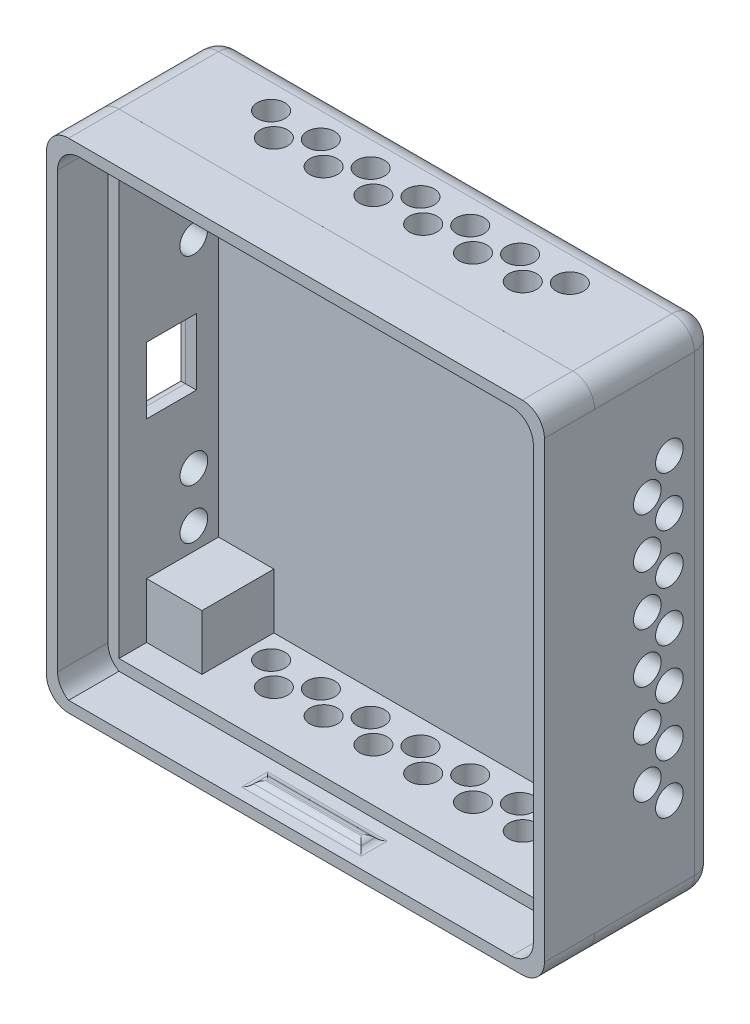
SolidWorks part; units mm, degrees
ref_plane "Piano frontale" through (0, 0, 0) normal (0, 0, 1) x (1, 0, 0)
ref_plane "Piano superiore" through (0, 0, 0) normal (0, 1, 0) x (1, 0, 0)
ref_plane "Piano destro" through (0, 0, 0) normal (1, 0, 0) x (0, 0, -1)
sketch "Schizzo2" plane through (0, 0, 0) normal (0, 0, 1) x (1, 0, 0)
  line L1 (0, 0) -> (45, 0)
  line L2 (0, 0) -> (0, 45)
  line L3 (0, 45) -> (45, 45)
  line L4 (45, 0) -> (45, 45)
  dimension "D1" = 45
  dimension "D2" = 45
extrude "Estrusione-Estrusione2" add sketch "Schizzo2" along normal blind 11
shell "Svuota1" thickness 2 removed face at (22.5, 22.5, 11)
fillet "Raccordo1" radius 2 4 edges at (45, 45, 5.5) (45, 0, 5.5) (0, 0, 5.5) (0, 45, 5.5)
fillet "Raccordo2" radius 2 8 edges at (44.4142, 0.5858, 0) (22.5, 0, 0) (0.5858, 0.5858, 0) (0, 22.5, 0) (0.5858, 44.4142, 0) (22.5, 45, 0) (44.4142, 44.4142, 0) (45, 22.5, 0)
sketch "Schizzo3" plane through (0, 0, 2) normal (0, 0, 1) x (1, 0, 0)
  line L0 (43, 43) -> (2, 43) construction
  line L1 (2, 43) -> (7, 43)
  line L2 (2, 43) -> (2, 38)
  line L3 (2, 38) -> (7, 38)
  line L4 (7, 43) -> (7, 38)
  line L5 (43, 43) -> (2, 43) construction
  dimension "D1" = 5
  dimension "D2" = 5
extrude "Estrusione-Estrusione3" add sketch "Schizzo3" along normal blind 6.5
sketch "Schizzo4" plane through (0, 0, 2) normal (0, 0, 1) x (1, 0, 0)
  line L1 (43, 2) -> (38, 2)
  line L2 (43, 2) -> (43, 7)
  line L3 (43, 7) -> (38, 7)
  line L4 (38, 2) -> (38, 7)
  dimension "D1" = 5
  dimension "D2" = 5
extrude "Estrusione-Estrusione4" add sketch "Schizzo4" along normal blind 6.5
fillet "Raccordo3" radius 4 2 edges at (38, 7, 5.25) (7, 38, 5.25)
sketch "Schizzo5" plane through (0, 0, 2) normal (0, 0, 1) x (1, 0, 0)
  line L0 (43, 2) -> (43, 43) construction
  line L1 (43, 43) -> (38, 43)
  line L2 (43, 43) -> (43, 38)
  line L3 (43, 38) -> (38, 38)
  line L4 (38, 43) -> (38, 38)
  line L5 (43, 43) -> (7, 43) construction
  line L7 (2, 2) -> (7, 2)
  line L8 (2, 2) -> (2, 7)
  line L9 (2, 7) -> (7, 7)
  line L10 (7, 2) -> (7, 7)
  dimension "D1" = 5
  dimension "D2" = 5
  dimension "D3" = 5
  dimension "D4" = 5
extrude "Estrusione-Estrusione5" add sketch "Schizzo5" along normal blind 6.5 contours L2 L1 L4 L3 | L8 L7 L10 L9
sketch "Schizzo12" plane through (0, 0, 11) normal (0, 0, 1) x (1, 0, 0)
  line L1 (0, 44.9999) -> (45, 44.9999)
  line L2 (0, 44.9999) -> (0, 43.9999)
  line L3 (0, 43.9999) -> (45, 43.9999)
  line L4 (45, 44.9999) -> (45, 43.9999)
  dimension "D1" = 45
  dimension "D2" = 1
extrude "Estrusione-Estrusione7" add sketch "Schizzo12" along normal blind 4.55
sketch "Schizzo13" plane through (0, 0, 11) normal (0, 0, 1) x (1, 0, 0)
  line L1 (45, 43.9999) -> (44, 43.9999)
  line L2 (45, 43.9999) -> (45, -0.0001)
  line L3 (45, -0.0001) -> (44, -0.0001)
  line L4 (44, 43.9999) -> (44, -0.0001)
  dimension "D1" = 44
  dimension "D2" = 1
extrude "Estrusione-Estrusione10" add sketch "Schizzo13" along normal blind 4.55
sketch "Schizzo15" plane through (0, 0, 11) normal (0, 0, 1) x (1, 0, 0)
  line L1 (44, -0.0001) -> (2, -0.0001)
  line L2 (44, -0.0001) -> (44, 0.9999)
  line L3 (44, 0.9999) -> (2, 0.9999)
  line L4 (2, -0.0001) -> (2, 0.9999)
  dimension "D1" = 1
  dimension "D2" = 42
extrude "Estrusione-Estrusione11" add sketch "Schizzo15" along normal blind 4.55
fillet "Raccordo4" radius 2 1 edges at (45, -0.0001, 13.275)
fillet "Raccordo5" radius 2 1 edges at (45, 44.9999, 13.275)
sketch "Schizzo17" plane through (0, 0, 11) normal (0, 0, 1) x (1, 0, 0)
  line L1 (0, 43.9999) -> (1, 43.9999)
  line L2 (0, 43.9999) -> (0, -0.0001)
  line L3 (0, -0.0001) -> (1, -0.0001)
  line L4 (1, 43.9999) -> (1, -0.0001)
  dimension "D1" = 1
  dimension "D2" = 44
extrude "Estrusione-Estrusione13" add sketch "Schizzo17" along normal blind 4.55
fillet "Raccordo6" radius 2 1 edges at (0, 44.9999, 13.275)
fillet "Raccordo7" radius 2 1 edges at (44, 0.9999, 13.275)
fillet "Raccordo8" radius 2 1 edges at (44, 43.9999, 13.275)
fillet "Raccordo9" radius 2 1 edges at (1, 43.9999, 13.275)
sketch "Schizzo18" plane through (0, 0, 11) normal (0, 0, 1) x (1, 0, 0)
  line L0 (1, -0.0001) -> (1, 41.9999) construction
  line L1 (2, -0.0001) -> (1, -0.0001)
  line L2 (2, -0.0001) -> (2, 0.9995)
  line L3 (2, 0.9995) -> (1, 0.9995)
  line L4 (1, -0.0001) -> (1, 0.9995)
extrude "Estrusione-Estrusione14" add sketch "Schizzo18" along normal blind 4.55
fillet "Raccordo10" radius 2 1 edges at (0, -0.0001, 13.275)
fillet "Raccordo11" radius 2 1 edges at (1, 0.9995, 13.275)
sketch "Schizzo22" plane through (0, 0.9999, 0) normal (0, 1, 0) x (1, 0, 0)
  line L5 (17.0049, -12.5647) -> (27.0049, -12.5647)
  line L6 (17.0049, -12.5647) -> (17.0049, -14.1147)
  line L7 (17.0049, -14.1147) -> (27.0049, -14.1147)
  line L8 (27.0049, -12.5647) -> (27.0049, -14.1147)
  dimension "D1" = 1.55
  dimension "D2" = 10
extrude "Estrusione-Estrusione15" add sketch "Schizzo22" along normal blind 0.5
fillet "Raccordo17" radius 0.74 4 edges at (27.0049, 1.4999, 13.3397) (22.0049, 1.4999, 12.5647) (17.0049, 1.4999, 13.3397) (22.0049, 1.4999, 14.1147)
fillet "Raccordo18" radius 0.74 4 edges at (22.0049, 0.9999, 12.5647) (27.0049, 0.9999, 13.3397) (17.0049, 0.9999, 13.3397) (22.0049, 0.9999, 14.1147)
sketch "Schizzo30" plane through (0, 43.9999, 0) normal (0, -1, 0) x (1, 0, 0)
  line L1 (17.0049, 14.1147) -> (27.0049, 14.1147)
  line L2 (17.0049, 14.1147) -> (17.0049, 12.5647)
  line L3 (17.0049, 12.5647) -> (27.0049, 12.5647)
  line L4 (27.0049, 14.1147) -> (27.0049, 12.5647)
extrude "Estrusione-Estrusione20" add sketch "Schizzo30" along normal blind 0.5 draft 1
fillet "Raccordo19" radius 0.74 4 edges at (22.0049, 43.4999, 12.5735) (26.9962, 43.4999, 13.3397) (22.0049, 43.4999, 14.106) (17.0136, 43.4999, 13.3397)
fillet "Raccordo20" radius 0.74 4 edges at (17.0049, 43.9999, 13.3397) (22.0049, 43.9999, 12.5647) (27.0049, 43.9999, 13.3397) (22.0049, 43.9999, 14.1147)
sketch "Schizzo34" plane through (43, 0, 0) normal (-1, 0, 0) x (0, 0, 1)
  circle A0 centre (4.2516, 35.9994) radius 1.25
  circle A1 centre (4.2516, 31.5034) radius 1.25
  circle A2 centre (4.2516, 27.0032) radius 1.25
  circle A3 centre (4.2516, 22.5053) radius 1.25
  circle A4 centre (4.2516, 18.0015) radius 1.25
  circle A5 centre (4.2516, 13.5036) radius 1.25
  circle A6 centre (4.2516, 9.0038) radius 1.25
  point P19 (2.7113, 7)
  dimension "D1" = 2.5
  dimension "D2" = 2.5
  dimension "D3" = 2.5
  dimension "D4" = 2.5
  dimension "D5" = 2.5
  dimension "D6" = 2.5
  dimension "D7" = 2.5
extrude "Taglio-Estrusione7" cut sketch "Schizzo34" against normal blind 2
sketch "Schizzo35" plane through (43, 0, 0) normal (-1, 0, 0) x (0, 0, 1)
  circle A0 centre (6.2524, 33.7503) radius 1.25
  circle A1 centre (6.2524, 29.2487) radius 1.25
  circle A2 centre (6.2524, 24.7505) radius 1.25
  circle A3 centre (6.2524, 20.2517) radius 1.25
  circle A4 centre (6.2524, 15.7547) radius 1.25
  circle A5 centre (6.2524, 11.252) radius 1.25
  dimension "D1" = 2.5
  dimension "D2" = 2.5
  dimension "D3" = 2.5
  dimension "D4" = 2.5
  dimension "D5" = 2.5
  dimension "D6" = 2.5
extrude "Taglio-Estrusione8" cut sketch "Schizzo35" against normal blind 2
sketch "Schizzo36" plane through (0, 2, 0) normal (0, 1, 0) x (1, 0, 0)
  circle A0 centre (35.9868, -4.2536) radius 1.25
  circle A1 centre (31.4911, -4.2536) radius 1.25
  circle A2 centre (26.996, -4.2536) radius 1.25
  circle A3 centre (22.4971, -4.2536) radius 1.25
  circle A4 centre (17.9983, -4.2536) radius 1.25
  circle A5 centre (13.4999, -4.2536) radius 1.25
  circle A6 centre (9.0039, -4.2536) radius 1.25
  dimension "D1" = 2.5
  dimension "D2" = 2.5
  dimension "D3" = 2.5
  dimension "D4" = 2.5
  dimension "D5" = 2.5
  dimension "D6" = 2.5
  dimension "D7" = 2.5
extrude "Taglio-Estrusione9" cut sketch "Schizzo36" against normal blind 2
sketch "Schizzo37" plane through (0, 2, 0) normal (0, 1, 0) x (1, 0, 0)
  circle A0 centre (33.7463, -6.2534) radius 1.25
  circle A1 centre (29.2472, -6.2534) radius 1.25
  circle A2 centre (24.7485, -6.2534) radius 1.25
  circle A3 centre (20.2458, -6.2534) radius 1.25
  circle A4 centre (15.749, -6.2534) radius 1.25
  circle A5 centre (11.2492, -6.2534) radius 1.25
  point P17 (7, -3.2646)
  dimension "D1" = 2.5
  dimension "D2" = 2.5
  dimension "D3" = 2.5
  dimension "D4" = 2.5
  dimension "D5" = 2.5
  dimension "D6" = 2.5
extrude "Taglio-Estrusione10" cut sketch "Schizzo37" against normal blind 2
sketch "Schizzo38" plane through (0, 43, 0) normal (0, -1, 0) x (-1, 0, 0)
  circle A0 centre (-8.9935, -4.2481) radius 1.25
  circle A1 centre (-13.4899, -4.2481) radius 1.25
  circle A2 centre (-17.9905, -4.2481) radius 1.25
  circle A3 centre (-22.4934, -4.2481) radius 1.25
  circle A4 centre (-26.9933, -4.2481) radius 1.25
  circle A5 centre (-31.495, -4.2481) radius 1.25
  circle A6 centre (-35.9965, -4.2481) radius 1.25
  dimension "D1" = 2.5
  dimension "D2" = 2.5
  dimension "D3" = 2.5
  dimension "D4" = 2.5
  dimension "D5" = 2.5
  dimension "D6" = 2.5
  dimension "D7" = 2.5
extrude "Taglio-Estrusione11" cut sketch "Schizzo38" against normal blind 2
sketch "Schizzo39" plane through (0, 43, 0) normal (0, -1, 0) x (-1, 0, 0)
  circle A0 centre (-11.2508, -6.2534) radius 1.25
  circle A1 centre (-15.7484, -6.2534) radius 1.25
  circle A2 centre (-20.2458, -6.2534) radius 1.25
  circle A3 centre (-24.7485, -6.2534) radius 1.25
  circle A4 centre (-29.2472, -6.2534) radius 1.25
  circle A5 centre (-33.7463, -6.2534) radius 1.25
  dimension "D1" = 2.5
  dimension "D2" = 2.5
  dimension "D3" = 2.5
  dimension "D4" = 2.5
  dimension "D5" = 2.5
  dimension "D6" = 2.5
extrude "Taglio-Estrusione12" cut sketch "Schizzo39" against normal blind 2
sketch "Schizzo40" plane through (2, 0, 0) normal (1, 0, 0) x (0, 0, -1)
  circle A0 centre (-4.2347, 8.9988) radius 1.25
  circle A1 centre (-4.2347, 13.4961) radius 1.25
  circle A2 centre (-4.2527, 35.9982) radius 1.25
  circle A3 centre (-4.2527, 31.4945) radius 1.25
  dimension "D1" = 2.5
  dimension "D2" = 2.5
  dimension "D5" = 2.5
  dimension "D6" = 2.5
sketch "Schizzo42" plane through (2, 0, 0) normal (1, 0, 0) x (0, 0, -1)
  line L0 (-8.5, 25.5052) -> (-4, 25.5052)
  line L5 (-8.5, 25.5052) -> (-8.5, 19.5052)
  line L6 (-8.5, 19.5052) -> (-4, 19.5052)
  line L7 (-4, 25.5052) -> (-4, 19.5052)
  dimension "D1" = 6
  dimension "D2" = 4.5
extrude "Taglio-Estrusione13" cut sketch "Schizzo42" against normal blind 2
fillet "Raccordo21" radius 1 4 edges at (0, 19.5052, 6.25) (0, 22.5052, 4) (0, 25.5052, 6.25) (0, 22.5052, 8.5)
extrude "Taglio-Estrusione14" cut sketch "Schizzo40" against normal blind 2
